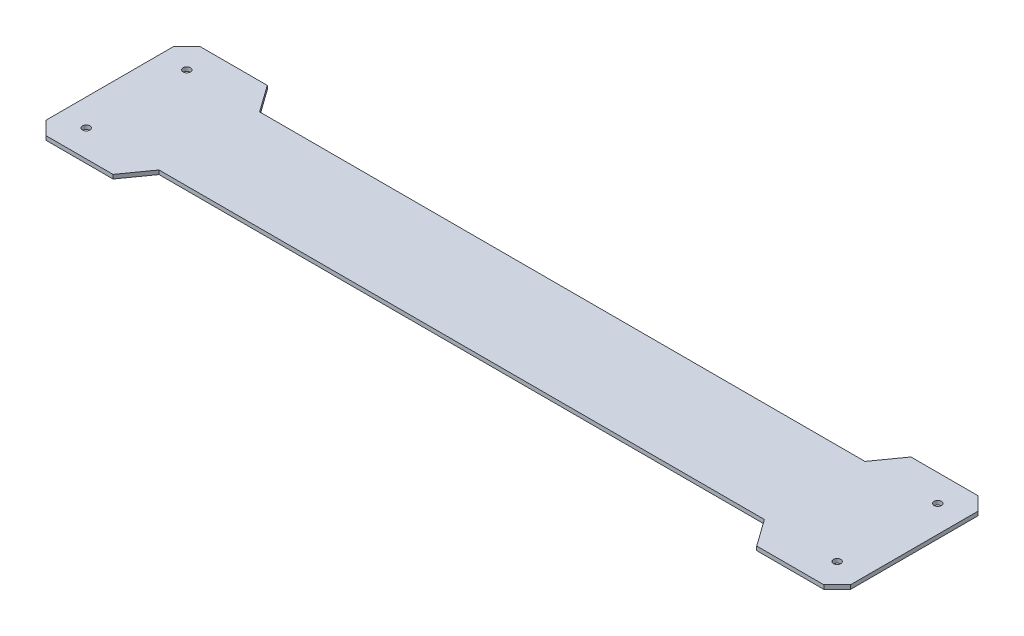
SolidWorks part; units mm, degrees
ref_plane "Front Plane" through (0, 0, 0) normal (0, 0, 1) x (1, 0, 0)
ref_plane "Top Plane" through (0, 0, 0) normal (0, 1, 0) x (1, 0, 0)
ref_plane "Right Plane" through (0, 0, 0) normal (1, 0, 0) x (0, 0, -1)
sketch "Sketch1" plane through (0, 0, 0) normal (0, 1, 0) x (1, 0, 0)
  line L0 (44.6193, 0) -> (44.6193, -115) construction
  line L1 (14.6193, 0) -> (64.6193, 0)
  line L2 (4.6193, -10) -> (4.6193, -105)
  line L3 (14.6193, -115) -> (64.6193, -115)
  line L4 (564.6193, 0) -> (564.6193, -115) construction
  line L5 (78.8949, -95) -> (64.6193, -115)
  line L6 (4.6193, -10) -> (14.6193, 0)
  line L7 (4.6193, -105) -> (14.6193, -115)
  line L8 (78.8949, -95) -> (530.3437, -95)
  line L9 (78.8949, -20) -> (530.3437, -20)
  line L10 (78.8949, -20) -> (64.6193, 0)
  line L11 (304.6193, 0) -> (304.6193, -115) construction
  line L12 (530.3437, -20) -> (544.6193, 0)
  line L13 (604.6193, -105) -> (594.6193, -115)
  line L14 (604.6193, -10) -> (594.6193, 0)
  line L15 (530.3437, -95) -> (544.6193, -115)
  line L16 (594.6193, -115) -> (544.6193, -115)
  line L17 (604.6193, -10) -> (604.6193, -105)
  line L18 (594.6193, 0) -> (544.6193, 0)
  circle A0 centre (24.6193, -20) radius 2.75
  circle A1 centre (24.6193, -95) radius 2.75
  circle A2 centre (584.6193, -95) radius 2.75
  circle A3 centre (584.6193, -20) radius 2.75
  point P0 (4.6193, 0)
  point P2 (4.6193, -115)
  point P28 (304.6193, -20)
  point P29 (304.6193, -95)
  point P34 (604.6193, -115)
  point P35 (604.6193, 0)
  dimension "D4" = 5.5
  dimension "D5" = 20
  dimension "D1" = 115
  dimension "D2" = 300
  dimension "D3" = 40
  dimension "D6" = 20
  dimension "D7" = 20
  dimension "D8" = 20
  dimension "D9" = 20
  dimension "D10" = 20
extrude "Boss-Extrude1" add sketch "Sketch1" along normal blind 3
